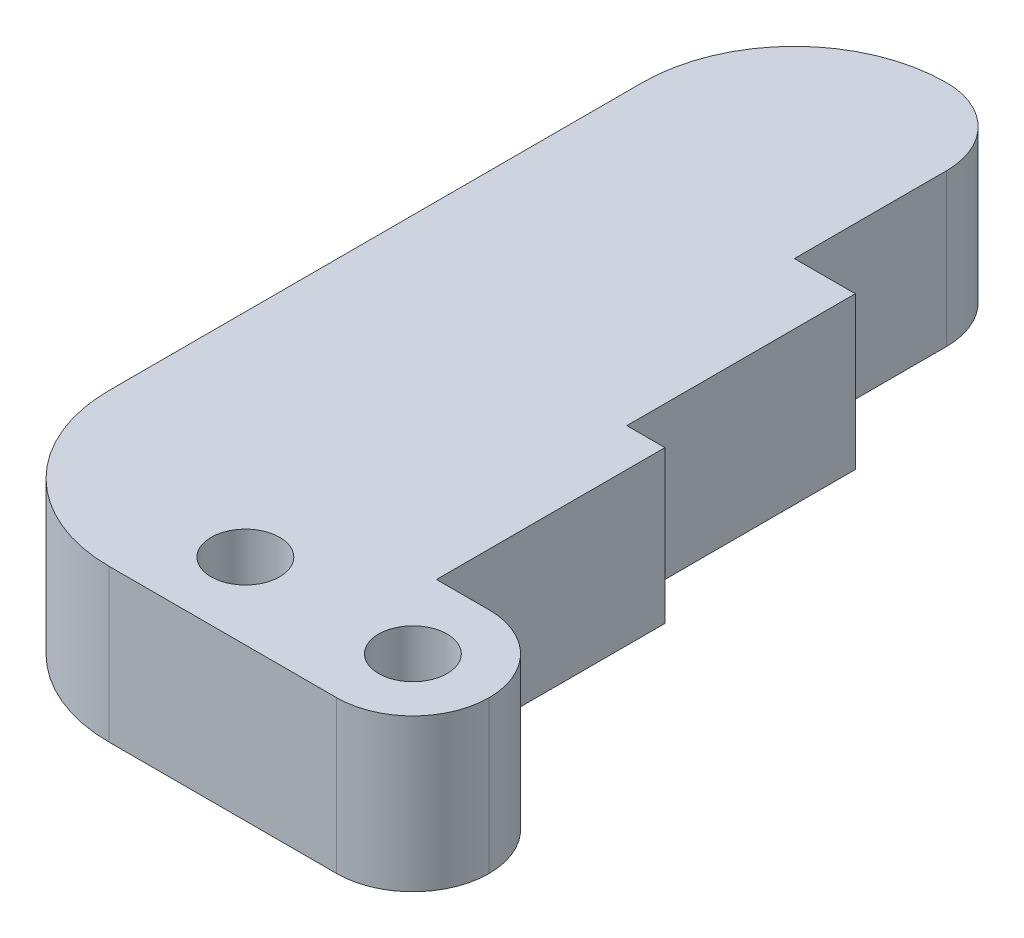
SolidWorks part; units mm, degrees
ref_plane "Front Plane" through (0, 0, 0) normal (0, 0, 1) x (1, 0, 0)
ref_plane "Top Plane" through (0, 0, 0) normal (0, 1, 0) x (1, 0, 0)
ref_plane "Right Plane" through (0, 0, 0) normal (1, 0, 0) x (0, 0, -1)
sketch "Sketch1" plane through (0, 0, 0) normal (0, 1, 0) x (1, 0, 0)
  line L0 (-100, 0) -> (100, 0) construction
  line L1 (0, -100) -> (0, 100) construction
  point P4 (0, 0)
  point P8 (0, 0)
  dimension "D1" = 200
sketch "Sketch2" plane through (0, 0, 0) normal (0, 1, 0) x (1, 0, 0)
  line L0 (-8.45, 15) -> (-8.45, 0)
  line L1 (0, -100) -> (0, 100) construction
  line L3 (-100, 0) -> (100, 0) construction
  line L5 (-8.45, 15) -> (-10.95, 15)
  line L6 (-10.95, 15) -> (-10.95, 30)
  line L7 (-10.95, 30) -> (-14.95, 30)
  line L8 (-14.95, 30) -> (-14.95, 45)
  line L9 (-14.95, 45) -> (-29.95, 45)
  line L16 (-8.45, 0) -> (0, 0)
  line L17 (0, 0) -> (0, -10)
  line L18 (0, -10) -> (-29.95, -10)
  line L19 (-29.95, 45) -> (-29.95, -10)
  circle A0 centre (0, 8.5) radius 8.5 construction
  circle A1 centre (0, 25) radius 11 construction
  circle A3 centre (0, 42) radius 15 construction
  dimension "D1" = 17
  dimension "D5" = 22
  dimension "D7" = 10.95
  dimension "D8" = 30
  dimension "D2" = 10
  dimension "D3" = 15
  dimension "D6" = 15
  dimension "D9" = 42
  dimension "D10" = 14.95
  dimension "D11" = 8.45
extrude "Boss-Extrude1" add sketch "Sketch2" along normal blind 10
sketch "Sketch3" plane through (0, 10, 0) normal (0, 1, 0) x (1, 0, 0)
  line L0 (-16, -5) -> (-5, -5) construction
  line L1 (0, -10) -> (0, 0) construction
  line L2 (0, -100) -> (0, 100) construction
  circle A0 centre (-16, -5) radius 2.25
  circle A1 centre (-5, -5) radius 2.25
  point P4 (0, 0)
  point P7 (0, -5)
  point P10 (-5, -5)
  dimension "D1" = 4.5
  dimension "D2" = 11
  dimension "D3" = 5
extrude "Cut-Extrude1" cut sketch "Sketch3" against normal blind 10
fillet "Fillet1" radius 10 2 edges at (-29.95, 5, -45) (-29.95, 5, 10)
fillet "Fillet2" radius 5 3 edges at (-14.95, 5, -45) (0, 5, 0) (0, 5, 10)
